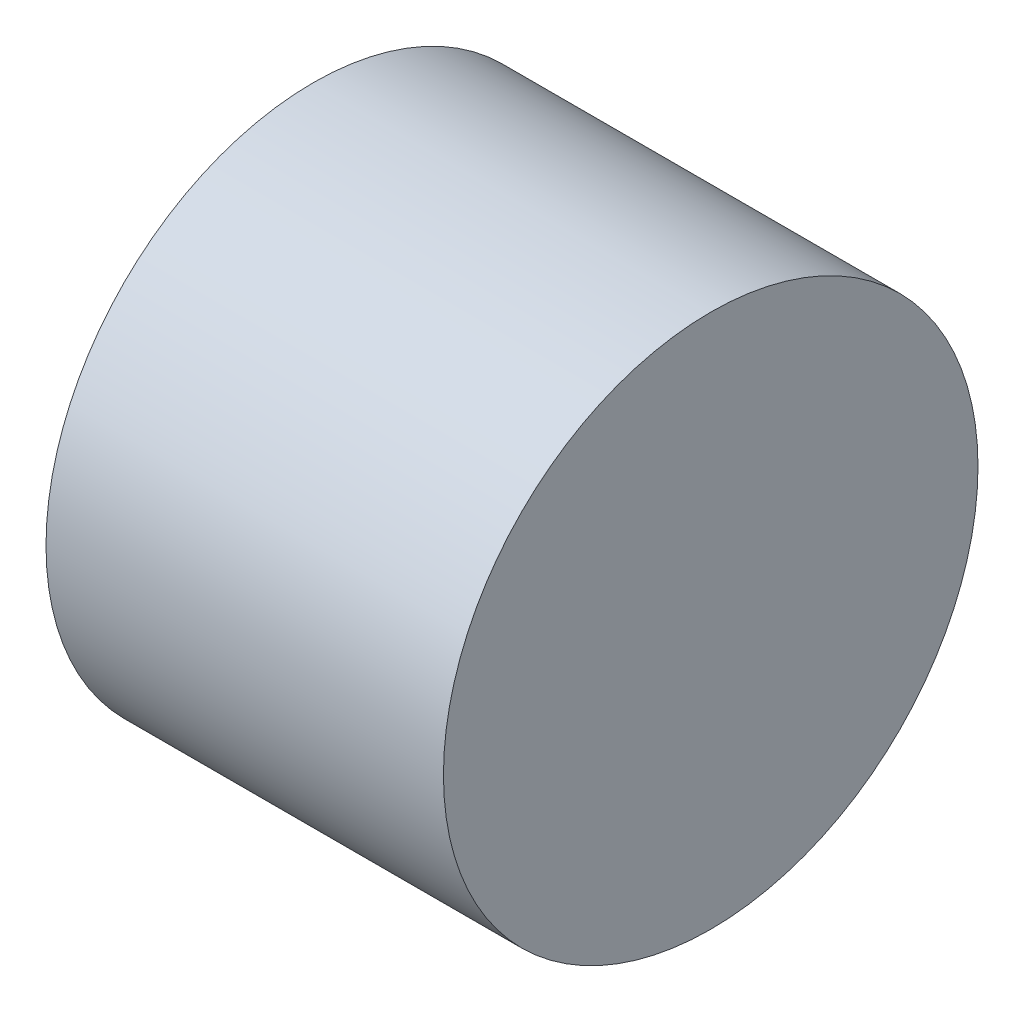
SolidWorks part; units mm, degrees
ref_plane "Front Plane" through (0, 0, 0) normal (0, 0, 1) x (1, 0, 0)
ref_plane "Top Plane" through (0, 0, 0) normal (0, 1, 0) x (1, 0, 0)
ref_plane "Right Plane" through (0, 0, 0) normal (1, 0, 0) x (0, 0, -1)
sketch "Leg_Stop_Plug Sketch" plane through (0, 0, 0) normal (0, 0, 1) x (1, 0, 0)
  line L0 (-3000, 0) -> (3000, 0) construction
  line L1 (1090, 9) -> (1090, 13.45)
  line L2 (1090, 13.45) -> (1110, 13.45)
  line L3 (1110, 13.45) -> (1110, 0)
  line L4 (1110, 0) -> (1104, 0)
  line L5 (1104, 0) -> (1104, 9)
  line L6 (1104, 9) -> (1090, 9)
revolve "Leg_Stop_Plug" add sketch "Leg_Stop_Plug Sketch" angle 360 about L0
ref_axis "Engine Axis" through (1111, 0, 0) along (-1, 0, 0)
